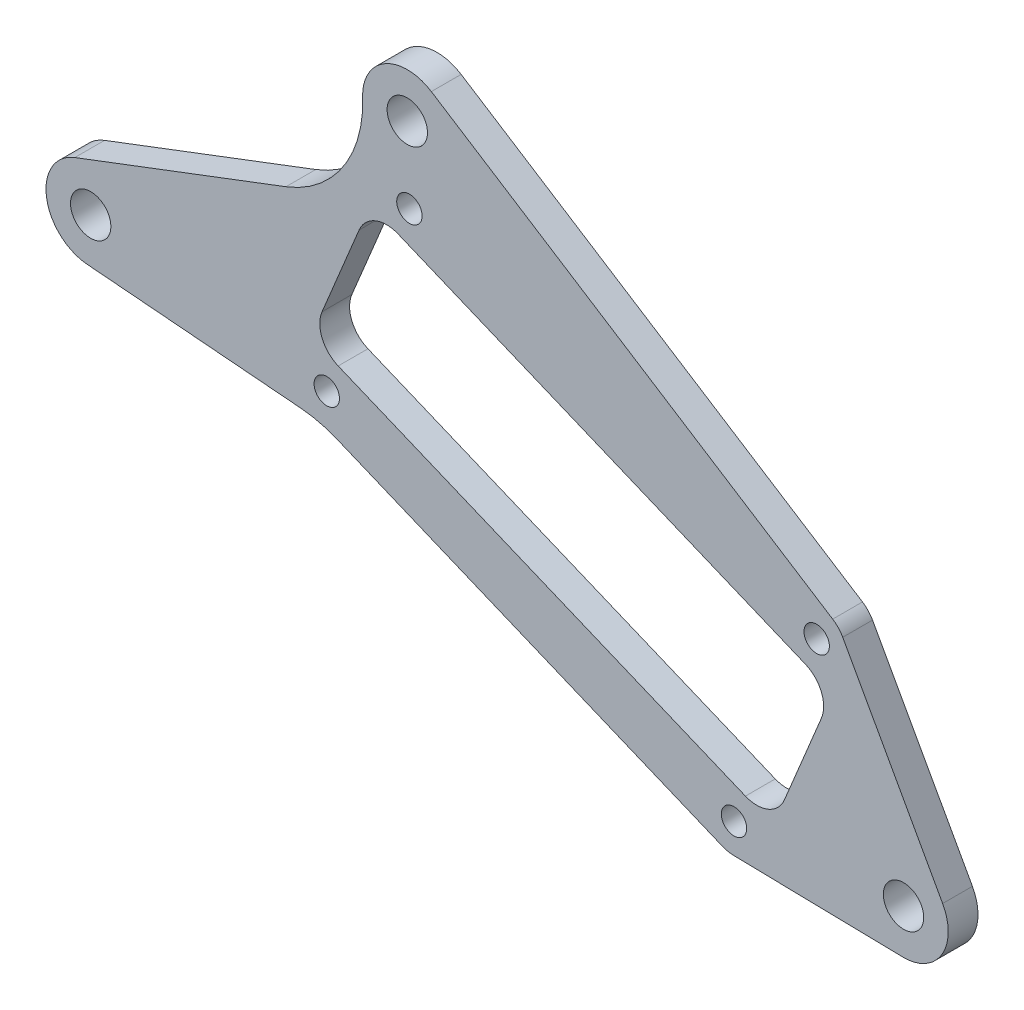
SolidWorks part; units mm, degrees
material "ABS PC"
ref_plane "Front Plane" through (0, 0, 0) normal (0, 0, 1) x (1, 0, 0)
ref_plane "Top Plane" through (0, 0, 0) normal (0, 1, 0) x (1, 0, 0)
ref_plane "Right Plane" through (0, 0, 0) normal (1, 0, 0) x (0, 0, -1)
sketch "Sketch1" plane through (0, 0, 0) normal (0, 0, 1) x (1, 0, 0)
  line L0 (80.1722, 1.0948) -> (90.8214, -18.1613)
  line L1 (86.5572, -25.2276) -> (68.5193, -24.8619)
  line L2 (33.9785, 17.5615) -> (68.5836, -21.6875) construction
  line L3 (33.9785, 17.5615) -> (25.1684, -3.6842) construction
  line L4 (29.5735, 6.9386) -> (51.2811, -2.063) construction
  line L5 (23.9522, -6.6171) -> (67.3674, -24.6204)
  line L6 (-0.3944, -4.7461) -> (24.9055, -6.8483)
  line L7 (-1.6929, 4.4514) -> (30.8862, 16.8417)
  line L8 (29.1149, 24.4508) -> (30.8862, 16.8417)
  line L9 (36.3158, 29.545) -> (79.102, 2.2345)
  line L10 (72.7326, -19.9709) -> (23.4517, 0.4648)
  line L11 (72.7326, -19.9709) -> (79.1104, -4.5908)
  line L12 (23.4517, 0.4648) -> (29.8295, 15.8449)
  line L13 (79.1104, -4.5908) -> (29.8295, 15.8449)
  line L14 (72.7326, -19.9709) -> (29.8295, 15.8449) construction
  line L15 (23.4517, 0.4648) -> (79.1104, -4.5908) construction
  circle A0 centre (0, 0) radius 4.7625
  circle A1 centre (86.6537, -20.4661) radius 4.7625
  circle A2 centre (33.7534, 25.5306) radius 4.7625
  circle A3 centre (33.9785, 17.5615) radius 3.175
  circle A4 centre (77.3937, -0.4418) radius 3.175
  circle A5 centre (68.5836, -21.6875) radius 3.175
  circle A6 centre (25.1684, -3.6842) radius 3.175
  circle A7 centre (68.5836, -21.6875) radius 1.6 construction
  circle A8 centre (77.3937, -0.4418) radius 1.6 construction
  circle A9 centre (33.9785, 17.5615) radius 1.6 construction
  circle A10 centre (25.1684, -3.6842) radius 1.6 construction
  point P27 (0, 0)
  point P42 (0, 0)
  point P46 (0, 0)
  point P49 (0, 0)
  dimension "D1" = 9.525
  dimension "D4" = 6.35
  dimension "D2" = 3.175
  dimension "D3" = 3.175
extrude "Boss-Extrude1" add sketch "Sketch1" along normal blind 3.175 contours A0 | A6 | A3 | A2 | A4 | A1 | A5 | A6 L6 L5 A5 L1 A1 L0 A4 L9 A2 L8 A3 L7 A0 | A6 L5 L6 | A4 L9 A2 L8 A3 L13 | A6 L6 L5 A5 L10 | A5 L1 A1 L0 A4 L11 region at (79.7971, -15.0988, 0) region at (77.3937, -0.4418, 0) region at (86.6537, -20.4661, 0) region at (53.516, 12.1256, 0) region at (33.7534, 25.5306, 0) region at (68.5836, -21.6875, 0) region at (15.7152, 3.4641, 0) region at (33.9785, 17.5615, 0) region at (46.8771, -12.6862, 0) region at (24.418, -6.7773, 0) region at (0, 0, 0) region at (25.1684, -3.6842, 0)
fillet "Fillet1" radius 3.175 4 edges at (72.7326, -19.9709, 1.5875) (79.1104, -4.5908, 1.5875) (23.4517, 0.4648, 1.5875) (29.8295, 15.8449, 1.5875)
hole_wizard "#6 Clearance Hole1" positions "Sketch2" profile "Sketch3" hole size "#6" standard "ANSI Inch" end condition through all
sketch "Sketch2" plane through (0, 0, 3.175) normal (0, 0, 1) x (1, 0, 0)
  point P0 (0, 0)
  point P3 (33.7534, 25.5306)
  point P6 (86.6537, -20.4661)
sketch "Sketch3" plane through (0, 0, 3.175) normal (1, 0, 0) x (0, -1, 0)
  line L0 (0, 0) -> (0, 3.175)
  line L1 (0, 3.175) -> (2.1526, 3.175)
  line L2 (2.1526, 3.175) -> (2.1526, 0)
  line L5 (2.1526, 0) -> (0, 0)
  line L11 (0, -6.35) -> (0, 107.95) construction
  dimension "Thru Hole Dia." = 4.3053
  dimension "Thru Hole Depth" = 3.175
hole_wizard "#2 Clearance Hole1" positions "Sketch4" profile "Sketch5" hole size "#2" standard "ANSI Inch" end condition through all
sketch "Sketch4" plane through (0, 0, 3.175) normal (0, 0, 1) x (1, 0, 0)
  point P1 (33.9785, 17.5615)
  point P4 (77.3937, -0.4418)
  point P7 (68.5836, -21.6875)
  point P10 (25.1684, -3.6842)
sketch "Sketch5" plane through (33.9785, 17.5615, 3.175) normal (1, 0, 0) x (0, -1, 0)
  line L0 (0, 0) -> (0, 3.175)
  line L1 (0, 3.175) -> (1.3525, 3.175)
  line L2 (1.3525, 3.175) -> (1.3525, 0)
  line L5 (1.3525, 0) -> (0, 0)
  line L11 (0, -6.35) -> (0, 107.95) construction
  dimension "Thru Hole Dia." = 2.7051
  dimension "Thru Hole Depth" = 3.175
fillet "Fillet2" radius 12.7 2 edges at (24.4108, -6.8072, 1.5875) (30.8862, 16.8417, 1.5875)
